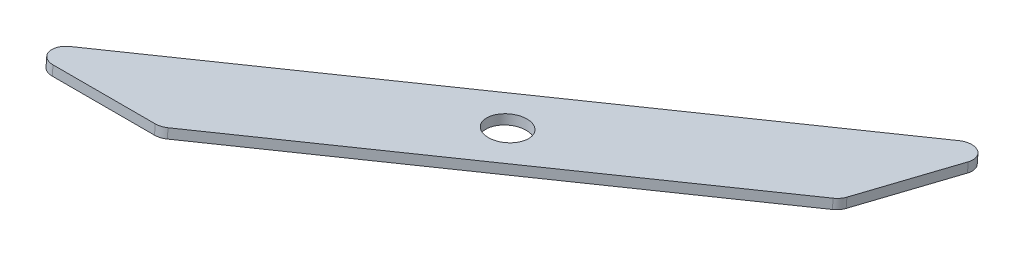
SolidWorks part; units mm, degrees
material "Plain Carbon Steel"
ref_plane "Front Plane" through (0, 0, 0) normal (0, 0, 1) x (1, 0, 0)
ref_plane "Top Plane" through (0, 0, 0) normal (0, 1, 0) x (1, 0, 0)
ref_plane "Right Plane" through (0, 0, 0) normal (1, 0, 0) x (0, 0, -1)
ref_axis "Axis1" through (323.2409, 73.7808, 63.5779) along (-0.2127, 0.0811, 0.9737)
ref_axis "Axis2" through (-330.1109, 71.1626, 32.129) along (0.2127, 0.0811, 0.9737)
ref_axis "Axis3" through (201.261, 120.6089, 629.197) along (-1, 0, 0)
ref_plane "Plane1" through (0, 68.0164, -5.6624) normal (0, 0.9966, -0.083) x (1, 0, 0)
ref_plane "Plane2" through (0, 55.3602, -4.6088) normal (0, -0.9966, 0.083) x (-1, 0, 0)
sketch "Sketch1" plane through (0, 55.3602, -4.6088) normal (0, -0.9966, 0.083) x (-1, 0, 0)
  line L0 (-210.8189, -585.8957) -> (-147.3502, -637.034)
  line L1 (-323.2409, -69.4798) -> (-207.2107, -602.4702) construction
  line L2 (-201.261, -637.034) -> (201.2079, -637.034) construction
  line L3 (-147.3502, -637.034) -> (-122.0477, -637.034)
  line L4 (-122.0477, -637.034) -> (-216.2011, -561.1724)
  line L5 (-216.2011, -561.1724) -> (-210.8189, -585.8957)
  line L6 (-213.51, -573.534) -> (-134.699, -637.034) construction
  line L7 (-216.2011, -561.1724) -> (-147.3502, -637.034) construction
  line L8 (-122.0477, -637.034) -> (-210.8189, -585.8957) construction
  circle A0 centre (-174.1045, -605.284) radius 3.2639
  point P10 (-212.579, -577.8107)
  dimension "D2" = 6.5278
  dimension "D3" = 31.75
  dimension "D1" = 15.875
extrude "Boss-Extrude1" add sketch "Sketch1" along normal blind 1.5875
fillet "Fillet1" radius 2.54 4 edges at (122.0477, 107.4201, 630.295) (147.3502, 107.4201, 630.295) (210.8189, 103.1775, 579.333) (216.2011, 101.1263, 554.6948)
